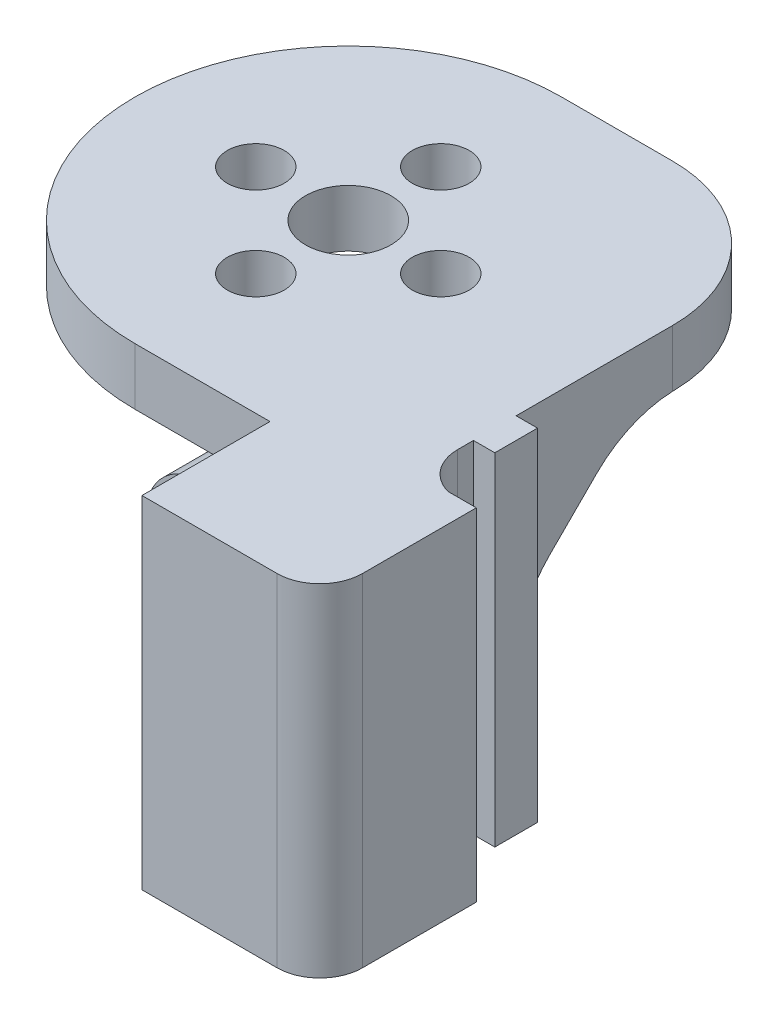
SolidWorks part; units mm, degrees
ref_plane "Front Plane" through (0, 0, 0) normal (0, 0, 1) x (1, 0, 0)
ref_plane "Top Plane" through (0, 0, 0) normal (0, 1, 0) x (1, 0, 0)
ref_plane "Right Plane" through (0, 0, 0) normal (1, 0, 0) x (0, 0, -1)
sketch "Sketch1" plane through (0, 0, 0) normal (0, 1, 0) x (1, 0, 0)
  line L1 (10, -15) -> (-10, -15)
  line L2 (10, -15) -> (10, 15)
  line L3 (10, 15) -> (-10, 15)
  line L5 (10, -15) -> (-10, 15) construction
  line L6 (10, 15) -> (-10, -15) construction
  arc A0 (-10, 15) -> (-10, -15) centre (-10, 0) ccw
  circle A1 centre (-10, 0) radius 3
  circle A2 centre (-10, 6.5) radius 2
  circle A3 centre (-3.5, 0) radius 2
  circle A4 centre (-10, -6.5) radius 2
  circle A5 centre (-16.5, 0) radius 2
  point P0 (0, 0)
  point P18 (-10, 0)
  dimension "D3" = 15
  dimension "D4" = 6
  dimension "D5" = 6.5
  dimension "D1" = 20
  dimension "D2" = 30
  dimension "D6" = 4
extrude "Boss-Extrude1" add sketch "Sketch1" along normal blind 4
sketch "Sketch5" plane through (0, 0, 15) normal (0, 0, 1) x (1, 0, 0)
  line L0 (-10, 4) -> (10, 4) construction
  line L1 (10, 0) -> (-0.5, 0)
  line L2 (10, 0) -> (10, 4)
  line L3 (10, 4) -> (-0.5, 4)
  line L4 (-0.5, 0) -> (-0.5, 4)
  dimension "D1" = 10.5
extrude "Boss-Extrude3" add sketch "Sketch5" along normal blind 9
sketch "Sketch6" plane through (0, 0, 0) normal (0, -1, 0) x (-1, 0, 0)
  line L0 (-10, -24) -> (-10, 15) construction
  line L1 (0.5, -24) -> (-10, -24)
  line L2 (0.5, -24) -> (0.5, -21)
  line L3 (0.5, -21) -> (-10, -21)
  line L4 (-10, -24) -> (-10, -21)
  dimension "D1" = 3
extrude "Boss-Extrude4" add sketch "Sketch6" along normal blind 20
sketch "Sketch7" plane through (0, 0, 0) normal (0, -1, 0) x (-1, 0, 0)
  line L0 (-6.7, -21) -> (-10, -21)
  line L1 (-10, -21) -> (-10, 15) construction
  line L2 (-6.7, -21) -> (-7, -13)
  line L3 (0.5, -21) -> (-10, -21) construction
  line L4 (-10, -21) -> (-10, -13)
  line L5 (-7, -13) -> (-10, -13)
  line L10 (-10, -21) -> (0.5, -21)
  line L11 (0.5, -21) -> (0.5, -15)
  line L12 (0.5, -15) -> (10, -15)
  line L13 (10, 15) -> (-10, 15)
  line L14 (-10, 15) -> (-10, -21)
  line L17 (0.5, -15) -> (10, -15)
  line L18 (10, 15) -> (-10, 15)
  line L19 (-10, 15) -> (-10, -21)
  arc A1 (10, -15) -> (10, 15) centre (10, 0) ccw
  arc A2 (10, -15) -> (10, 15) centre (10, 0) ccw
  line M6 (-10, -21) -> (0.5, -21)
  line M11 (-10, 15) -> (-10, -21)
  dimension "D1" = 3
  dimension "D2" = 0
  dimension "D3" = 3.3
  dimension "D4" = 8
extrude "Boss-Extrude5" add sketch "Sketch7" along normal blind 20 contours L2 L5 M11 M6 region at (8.4238, 0, 17.0635)
sketch "Sketch8" plane through (0, 0, 0) normal (0, -1, 0) x (1, 0, 0)
  line L0 (-0.5, 21) -> (-0.5, 14)
  line L1 (-0.5, 21) -> (2.8, 21)
  line L2 (-0.5, 21) -> (6.7, 21) construction
  line L3 (-0.5, 14) -> (2.5, 14)
  line L4 (2.5, 14) -> (2.8, 21)
  dimension "D1" = 7
  dimension "D2" = 3.3
  dimension "D3" = 3
extrude "Boss-Extrude6" add sketch "Sketch8" along normal blind 20
fillet "Fillet2" radius 0.5 1 edges at (6.7, -10, 21)
fillet "Fillet3" radius 0.5 1 edges at (2.8, -10, 21)
sketch "Sketch11" plane through (0, 0, 0) normal (0, -1, 0) x (-1, 0, 0)
  line L1 (-7.8, -6) -> (0.2, -6)
  line L2 (-7.8, -6) -> (-7.8, -9)
  line L3 (-7.8, -9) -> (0.2, -9)
  line L4 (0.2, -6) -> (0.2, -9)
  dimension "D1" = 8
  dimension "D2" = 3
  dimension "D3" = 4
  dimension "D4" = 2.2
extrude "Boss-Extrude8" add sketch "Sketch11" along normal blind 20
ref_plane "Plane4" through (7.8, 0, 6) normal (1, 0, 0) x (0, 0, -1)
sketch "Sketch19" plane through (7.8, 0, 6) normal (1, 0, 0) x (0, 0, -1)
  line L0 (0, -8) -> (8, 0)
  line L1 (0, -20) -> (0, 0) construction
  dimension "D1" = 8
  dimension "D2" = 8
rib "Rib3" sketch "Sketch19" sketch "Sketch19" thickness 6 extrusion direction parallel to sketch draft on no parameters "D1"=6
fillet "Fillet6" radius 5 1 edges at (1.8, -4, 6)
sketch "Sketch20" plane through (0, 0, 0) normal (0, -1, 0) x (-1, 0, 0)
  line L0 (-7.8, 3.0711) -> (-7.8, 15) construction
  line L1 (-10, 15) -> (10, 15) construction
  line L2 (-7, -13) -> (-10, -13) construction
  line L3 (-10, 15) -> (-7.8, 15)
  line L4 (-10, 15) -> (-10, -13)
  line L5 (-10, -13) -> (-7.8, -13)
  line L6 (-7.8, 15) -> (-7.8, -13)
extrude "Cut-Extrude3" cut sketch "Sketch20" against normal blind 20
fillet "Fillet7" radius 0.5 1 edges at (7.4, 0, 13)
fillet "Fillet8" radius 0.5 1 edges at (1, 0, 14)
sketch "Sketch23" plane through (-0.2, 0, 0) normal (-1, 0, 0) x (0, 0, 1)
  line L0 (6, -20) -> (6, -8) construction
  line L1 (9, -20) -> (6, -20)
  line L2 (9, -20) -> (9, -8)
  line L3 (9, -8) -> (6, -8)
  line L4 (6, -20) -> (6, -8)
  dimension "D1" = 12
extrude "Boss-Extrude9" add sketch "Sketch23" along normal blind 15
sketch "Sketch25" plane through (0, 0, 9) normal (0, 0, 1) x (1, 0, 0)
  line L0 (-15.2, -14) -> (-0.5, -14) construction
  line L1 (-15.2, -20) -> (-15.2, -8) construction
  line L2 (-0.5, 4) -> (-0.5, -20) construction
  circle A0 centre (-7.85, -14) radius 2
extrude "Cut-Extrude4" cut sketch "Sketch25" against normal blind 15
sketch "Sketch27" plane through (-0.2, 0, 0) normal (-1, 0, 0) x (0, 0, 1)
  line L1 (6, 0) -> (9, 0)
  line L2 (6, 0) -> (6, -8)
  line L3 (6, -8) -> (9, -8)
  line L4 (9, 0) -> (9, -8)
extrude "Boss-Extrude10" add sketch "Sketch27" along normal blind 4
fillet "Fillet12" radius 8 2 edges at (3.8, -8, 6) (4.8, 0, -2)
fillet "Fillet13" radius 1 2 edges at (-4.2, -8, 7.5) (-4.2, 0, 7.5)
fillet "Fillet14" radius 4 2 edges at (-15.2, -20, 7.5) (-15.2, -8, 7.5)
fillet "Fillet18" radius 3 1 edges at (7.8, 1.75, 13)
sketch "Sketch29" plane through (10, 0, 0) normal (1, 0, 0) x (0, 0, -1)
  line L1 (-24, 4) -> (-13, 4)
  line L2 (-24, 4) -> (-24, -20)
  line L3 (-24, -20) -> (-13, -20)
  line L4 (-13, 4) -> (-13, -20)
extrude "Boss-Extrude12" add sketch "Sketch29" along normal blind 2
fillet "Fillet19" radius 3 1 edges at (12, -8, 24)
sketch "Sketch31" plane through (7.8, 0, 0) normal (1, 0, 0) x (0, 0, -1)
  line L0 (15, 4) -> (-10.1086, 4) construction
  line L1 (-6, -20) -> (-9, -20)
  line L2 (-6, -20) -> (-6, 4)
  line L3 (-6, 4) -> (-9, 4)
  line L4 (-9, -20) -> (-9, 4)
extrude "Boss-Extrude13" add sketch "Sketch31" along normal blind 1.5
fillet "Fillet20" radius 10 1 edges at (7.8, 2, -15)
